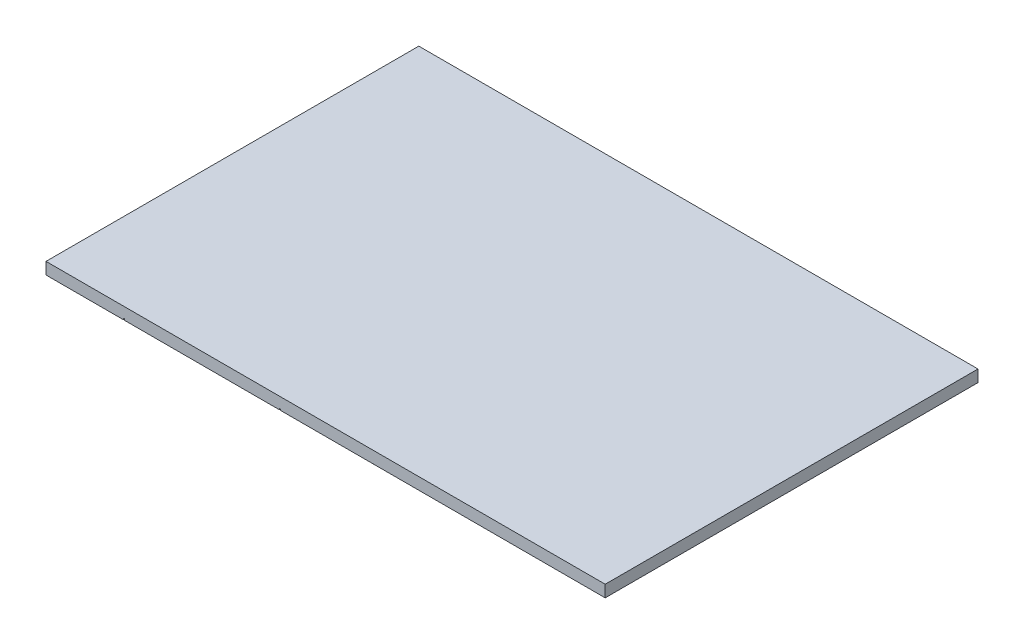
SolidWorks part; units mm, degrees
material "Акрил (Средняя-высокая ударопрочность)"
ref_plane "Спереди" through (0, 0, 0) normal (0, 0, 1) x (1, 0, 0)
ref_plane "Сверху" through (0, 0, 0) normal (0, 1, 0) x (1, 0, 0)
ref_plane "Справа" through (0, 0, 0) normal (1, 0, 0) x (0, 0, -1)
sketch "Эскиз1" plane through (0, 0, 0) normal (0, 1, 0) x (1, 0, 0)
  line L0 (6.5, -1.6073) -> (6.5, 77.9)
  line L12 (7.5, -1.6073) -> (7.5, 76.9)
  line L13 (8, 77.4) -> (24, 77.4)
  line L14 (7, 78.4) -> (25, 78.4)
  line L15 (24.5, 76.9) -> (24.5, 2.9)
  line L16 (25, 2.4) -> (43, 2.4)
  line L17 (25.5, 77.9) -> (25.5, 3.9)
  line L18 (26, 3.4) -> (42, 3.4)
  line L19 (42.5, 3.9) -> (42.5, 77.9)
  line L20 (43.5, 2.9) -> (43.5, 76.9)
  line L21 (43, 78.4) -> (61, 78.4)
  line L22 (44, 77.4) -> (60, 77.4)
  line L23 (60.5, 76.9) -> (60.5, 2.9)
  line L24 (61.5, 77.9) -> (61.5, 3.9)
  line L25 (61, 2.4) -> (79, 2.4)
  line L26 (62, 3.4) -> (78, 3.4)
  line L27 (78.5, 3.9) -> (78.5, 77.9)
  line L28 (79.5, 2.9) -> (79.5, 76.9)
  line L29 (79, 78.4) -> (97, 78.4)
  line L30 (80, 77.4) -> (96, 77.4)
  line L31 (96.5, 76.9) -> (96.5, 2.9)
  line L32 (97.5, 77.9) -> (97.5, 3.9)
  line L33 (97, 2.4) -> (115, 2.4)
  line L34 (98, 3.4) -> (114, 3.4)
  line L35 (114.5, 3.9) -> (114.5, 78.4)
  line L36 (115.5, 2.9) -> (115.5, 77.4)
  line L37 (114.5, 78.4) -> (114.5, 83)
  line L38 (114.5, 83) -> (115.5, 83)
  line L39 (115.5, 83) -> (115.5, 77.4)
  line L40 (6.5, -1.6073) -> (7.5, -1.6073)
  line L41 (15.8478, -3) -> (15.8478, 41)
  line L46 (-2, -2) -> (127, -2)
  line L47 (-2, -2) -> (-2, 84)
  line L48 (-2, 84) -> (127, 84)
  line L49 (127, -2) -> (127, 84)
  line L54 (16.1522, -3) -> (15.8478, -3)
  line L57 (16.1522, 41) -> (16.1522, -3)
  line L58 (15.8478, 41) -> (16.1522, 41)
  line L63 (70.35, 83) -> (70.3357, 41)
  line L64 (70.3357, 41) -> (70.6643, 41)
  line L65 (70.6643, 41) -> (70.65, 83)
  line L66 (70.65, 83) -> (70.35, 83)
  line L67 (51.8478, 41) -> (52.1522, 41)
  line L68 (52.1522, 41) -> (52.1522, -3)
  line L69 (52.1522, -3) -> (51.8478, -3)
  line L70 (51.8478, -3) -> (51.8478, 41)
  arc A0 (7.5, 76.9) -> (8, 77.4) centre (8, 76.9) cw
  arc A1 (6.5, 77.9) -> (7, 78.4) centre (7, 77.9) cw
  arc A2 (24.5, 76.9) -> (24, 77.4) centre (24, 76.9) ccw
  arc A3 (25.5, 77.9) -> (25, 78.4) centre (25, 77.9) ccw
  arc A4 (25, 2.4) -> (24.5, 2.9) centre (25, 2.9) cw
  arc A5 (26, 3.4) -> (25.5, 3.9) centre (26, 3.9) cw
  arc A6 (42, 3.4) -> (42.5, 3.9) centre (42, 3.9) ccw
  arc A7 (43.5, 2.9) -> (43, 2.4) centre (43, 2.9) cw
  arc A8 (43, 78.4) -> (42.5, 77.9) centre (43, 77.9) ccw
  arc A9 (43.5, 76.9) -> (44, 77.4) centre (44, 76.9) cw
  arc A10 (61.5, 77.9) -> (61, 78.4) centre (61, 77.9) ccw
  arc A11 (60.5, 76.9) -> (60, 77.4) centre (60, 76.9) ccw
  arc A12 (61, 2.4) -> (60.5, 2.9) centre (61, 2.9) cw
  arc A13 (62, 3.4) -> (61.5, 3.9) centre (62, 3.9) cw
  arc A14 (78.5, 3.9) -> (78, 3.4) centre (78, 3.9) cw
  arc A15 (79, 2.4) -> (79.5, 2.9) centre (79, 2.9) ccw
  arc A16 (79, 78.4) -> (78.5, 77.9) centre (79, 77.9) ccw
  arc A17 (79.5, 76.9) -> (80, 77.4) centre (80, 76.9) cw
  arc A18 (97.5, 77.9) -> (97, 78.4) centre (97, 77.9) ccw
  arc A19 (96.5, 76.9) -> (96, 77.4) centre (96, 76.9) ccw
  arc A20 (97, 2.4) -> (96.5, 2.9) centre (97, 2.9) cw
  arc A21 (98, 3.4) -> (97.5, 3.9) centre (98, 3.9) cw
  arc A22 (114.5, 3.9) -> (114, 3.4) centre (114, 3.9) cw
  arc A23 (115.5, 2.9) -> (115, 2.4) centre (115, 2.9) cw
  circle A26 centre (70.5, 41) radius 0.2
  ellipse E0 centre (16, 41) end of major axis (15.7978, 41) minor radius 0.2
  ellipse E1 centre (52, 41) end of major axis (51.7978, 41) minor radius 0.2
  point P4 (6.5, -1.6073)
  point P5 (7.5, -1.6073)
  point P6 (7.5, -1.6073)
  point P8 (0, 0)
  point P91 (0, 0)
  point P113 (0, 0)
  point P114 (0, 0)
  point P115 (0, 0)
  point P116 (0, 0)
  point P117 (0, 0)
  point P118 (0, 0)
  point P119 (0, 0)
  dimension "D2" = 0.5
  dimension "D3" = 0.5
  dimension "D4" = 0.5
  dimension "D5" = 0.5
  dimension "D6" = 0.5
  dimension "D7" = 0.5
  dimension "D8" = 0.5
  dimension "D9" = 0.5
  dimension "D10" = 0.5
  dimension "D11" = 0.5
  dimension "D12" = 0.5
  dimension "D13" = 0.5
  dimension "D14" = 0.5
  dimension "D15" = 0.5
  dimension "D16" = 0.5
  dimension "D17" = 0.5
  dimension "D18" = 0.5
  dimension "D19" = 0.5
  dimension "D20" = 0.5
  dimension "D21" = 0.5
  dimension "D22" = 0.5
  dimension "D23" = 0.5
  dimension "D24" = 0.5
  dimension "D25" = 0.5
  dimension "D26" = 2
  dimension "D1" = 3
extrude "Бобышка-Вытянуть2" add sketch "Эскиз1" along normal blind 2.73 contours L47 L46 L49 L48
extrude "Дорожки" cut sketch "Эскиз1<4>" along normal blind 1 contours L27 A16 L29 A18 L32 A21 L34 A22 L35 L37 L38 L39 L36 A23 L33 A20 L31 A19 L30 A17 L28 A15 L25 A12 L23 A11 L22 A9 L20 A7 L16 A4 L15 A2 L13 A0 L12 L40 L0 A1 L14 A3 L17 A5 L18 A6 L19 A8 L21 A10 L24 A13 L26 A14
sketch "Эскиз1<4>" plane through (0, 0, 0) normal (0, 1, 0) x (1, 0, 0) same geometry as "Эскиз1"
sketch "Эскиз5" plane through (0, 0, 0) normal (0, -1, 0) x (1, 0, 0)
sketch "Эскиз9" plane through (0, 0, 0) normal (0, 1, 0) x (1, 0, 0)
  line L41 (15.8478, -2) -> (15.8478, 41)
  line L54 (16.1522, -2) -> (15.8478, -2)
  line L57 (16.1522, 41) -> (16.1522, -2)
  line L58 (15.8478, 41) -> (16.1522, 41)
  line L63 (70.3643, 83) -> (70.3357, 41)
  line L64 (70.3357, 41) -> (70.6643, 41)
  line L65 (70.6643, 41) -> (70.6643, 83)
  line L66 (70.6643, 83) -> (70.3643, 83)
  line L67 (51.8478, 41) -> (52.1522, 41)
  line L68 (52.1522, 41) -> (52.1522, -2)
  line L69 (52.1522, -2) -> (51.8478, -2)
  line L70 (51.8478, -2) -> (51.8478, 41)
  circle A26 centre (70.5, 41) radius 0.2
  ellipse E0 centre (16, 41) end of major axis (15.7978, 41) minor radius 0.2
  ellipse E1 centre (52, 41) end of major axis (51.7978, 41) minor radius 0.2
  point P91 (0, 0)
  dimension "D26" = 2
extrude "Вырез-Вытянуть5" cut sketch "Эскиз1<7>" along normal blind 0.3 contours E0
sketch "Эскиз1<7>" plane through (0, 0, 0) normal (0, 1, 0) x (1, 0, 0) same geometry as "Эскиз1"
extrude "Вырез-Вытянуть15" cut sketch "Эскиз9" along normal blind 0.3 contours E0 L41 L54 L57 | E1 L70 L69 L68 | A26 L65 L66 L63 | L63 A26 L65 L64 | L68 E1 L70 L67 | L70 E1 L68 L67 | L65 A26 L63 L64 | L57 E0 L41 L58 | L41 E0 L57 L58 region at (16, 0, -19.4105) region at (16, 0, -41.0681) region at (16, 0, -40.9094) region at (70.5071, 0, -61.7713) region at (70.5, 0, -41.0889) region at (70.5, 0, -40.9255) region at (52, 0, -41.0681) region at (52, 0, -40.9094) region at (52, 0, -19.4105)
